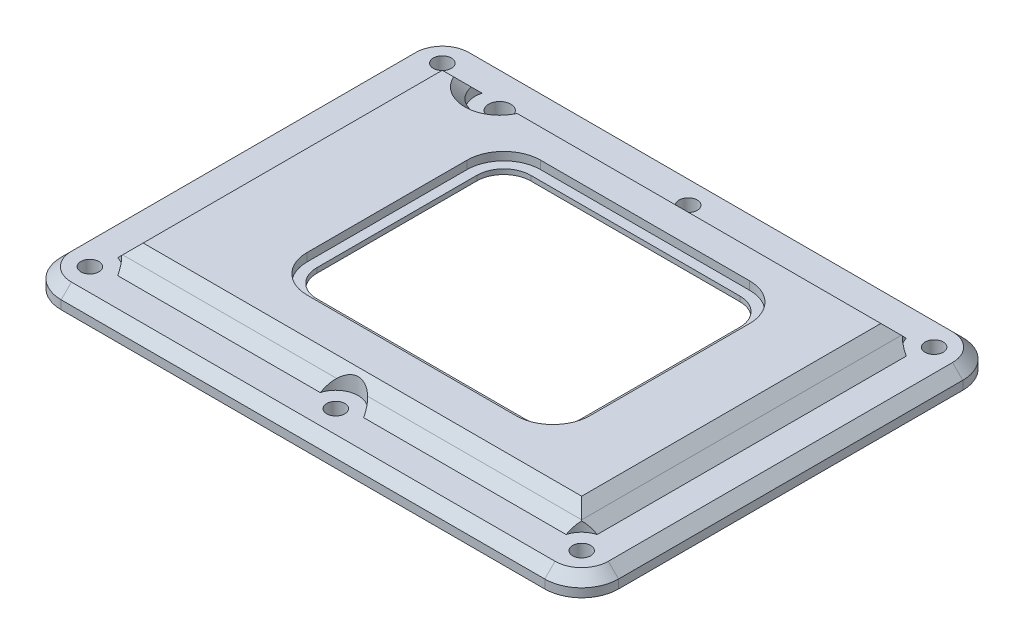
SolidWorks part; units mm, degrees
ref_plane "前视基准面" through (0, 0, 0) normal (0, 0, 1) x (1, 0, 0)
ref_plane "上视基准面" through (0, 0, 0) normal (0, 1, 0) x (1, 0, 0)
ref_plane "右视基准面" through (0, 0, 0) normal (1, 0, 0) x (0, 0, -1)
other "Configuration Table"
sketch "草图1" plane through (0, 0, 0) normal (0, 1, 0) x (1, 0, 0)
  line L1 (0, 0) -> (60, 0) construction
  line L2 (0, 0) -> (0, -43) construction
  line L3 (0, -43) -> (60, -43) construction
  line L4 (60, 0) -> (60, -43) construction
  line L5 (-4, 4) -> (64, 4)
  line L6 (-4, 4) -> (-4, -47)
  line L7 (-4, -47) -> (64, -47)
  line L8 (64, 4) -> (64, -47)
  line L9 (4, -4) -> (56, -4)
  line L10 (4, -4) -> (4, -39)
  line L11 (4, -39) -> (56, -39)
  line L12 (56, -4) -> (56, -39)
  circle A0 centre (0, 0) radius 1.1
  circle A1 centre (60, 0) radius 1.1
  circle A2 centre (30, 0) radius 1.1
  circle A3 centre (0, -43) radius 1.1
  circle A4 centre (60, -43) radius 1.1
  circle A5 centre (30, -43) radius 1.1
  dimension "D2" = 2.2
  dimension "D4" = 4
  dimension "D1" = 60
  dimension "D3" = 43
  dimension "D5" = 4
  dimension "D6" = 4
  dimension "D7" = 4
  dimension "D8" = 4
  dimension "D9" = 4
  dimension "D10" = 4
  dimension "D11" = 4
extrude "凸台-拉伸1" add sketch "草图1" along normal blind 2.31
sketch "草图2" plane through (0, 2.31, 0) normal (0, 1, 0) x (1, 0, 0)
  line L0 (2, -2) -> (58, -2)
  line L1 (4, -4) -> (56, -4)
  line L2 (4, -4) -> (4, -39)
  line L3 (4, -39) -> (56, -39)
  line L4 (56, -4) -> (56, -39)
  line L5 (58, -2) -> (58, -41)
  line L6 (2, -41) -> (58, -41)
  line L7 (2, -2) -> (2, -41)
  dimension "D1" = 2
extrude "凸台-拉伸2" add sketch "草图2" along normal blind 1.5
sketch "草图3" plane through (0, 2.31, 0) normal (0, 1, 0) x (1, 0, 0)
  circle A0 centre (8.5, -1.5) radius 1.35
  circle A2 centre (8.5, -1.5) radius 1.6 construction
  dimension "D2" = 2.7
extrude "切除-拉伸1" cut sketch "草图3" against normal up to next
sketch "草图4" plane through (0, 3.81, 0) normal (0, 1, 0) x (1, 0, 0)
  line L0 (4, -4) -> (4, -39) construction
  line L1 (14.25, -35.25) -> (48.75, -35.25)
  line L2 (14.25, -35.25) -> (14.25, -6.75)
  line L3 (14.25, -6.75) -> (48.75, -6.75)
  line L4 (48.75, -35.25) -> (48.75, -6.75)
  line L6 (56, -39) -> (56, -4) construction
  line L7 (56, -4) -> (4, -4) construction
  line L8 (4, -39) -> (56, -39) construction
  line L17 (2, -2) -> (2, -41)
  line L18 (2, -41) -> (58, -41)
  line L19 (58, -41) -> (58, -2)
  line L20 (58, -2) -> (2, -2)
  line L21 (2, -2) -> (2, -41)
  line L22 (2, -41) -> (58, -41)
  line L23 (58, -41) -> (58, -2)
  line L24 (58, -2) -> (2, -2)
  dimension "D1" = 10.25
  dimension "D2" = 7.25
  dimension "D3" = 2.75
  dimension "D4" = 3.75
  dimension "D5" = 0
extrude "凸台-拉伸3" add sketch "草图4" along normal blind 1
sketch "草图5" plane through (0, 2.31, 0) normal (0, 1, 0) x (1, 0, 0)
  circle A0 centre (8.5, -1.5) radius 3
  dimension "D1" = 6
extrude "切除-拉伸2" cut sketch "草图5" along normal up to next
sketch "草图6" plane through (0, 3.81, 0) normal (0, -1, 0) x (1, 0, 0)
  line L0 (5.3775, 4) -> (6.8417, 4)
  line L1 (6.8417, 4) -> (4, 4) construction
  line L2 (10.1583, 4) -> (11.6225, 4)
  arc A0 (11.6225, 4) -> (5.3775, 4) centre (8.5, 1.5) ccw
  arc A1 (10.1583, 4) -> (6.8417, 4) centre (8.5, 1.5) ccw construction
  arc A2 (10.1583, 4) -> (6.8417, 4) centre (8.5, 1.5) ccw
  dimension "D1" = 8
extrude "凸台-拉伸4" add sketch "草图6" along normal blind 2.5
sketch "草图7" plane through (0, 1.31, 0) normal (0, -1, 0) x (1, 0, 0)
  line L0 (5.3775, 4) -> (11.6225, 4)
  arc A0 (11.6225, 4) -> (5.3775, 4) centre (8.5, 1.5) ccw construction
  arc A1 (11.6225, 4) -> (5.3775, 4) centre (8.5, 1.5) ccw
extrude "凸台-拉伸5" add sketch "草图7" against normal up to surface (1 mm away) up to face at (19.25, 2.31, 12.2837)
fillet "圆角1" radius 4.5 8 edges at (48.75, 4.31, 6.75) (48.75, 4.31, 35.25) (14.25, 4.31, 35.25) (14.25, 4.31, 6.75) (-4, 1.155, 47) (64, 1.155, 47) (64, 1.155, -4) (-4, 1.155, -4)
chamfer "倒角1" distance 1.25 angle 45 19 edges at (58, 4.81, 21.5) (30, 4.81, 41) (2, 4.81, 21.5) (3.771, 4.81, 2) (34.729, 4.81, 2) (8.5, 4.81, 4.5) (3.771, 2.31, 2) (34.729, 2.31, 2) (2, 2.31, 21.5) (30, 2.31, 41) (58, 2.31, 21.5) (64, 2.31, 21.5) (62.682, 2.31, -2.682) (62.682, 2.31, 45.682) (30, 2.31, -4) (30, 2.31, 47) (-2.682, 2.31, -2.682) (-2.682, 2.31, 45.682) (-4, 2.31, 21.5)
sketch "草图9" plane through (0, 2.31, 0) normal (0, 1, 0) x (1, 0, 0)
  circle A0 centre (0, 0) radius 2.75
  circle A1 centre (30, 0) radius 2.75
  circle A2 centre (60, 0) radius 2.75
  circle A3 centre (60, -43) radius 2.75
  circle A4 centre (30, -43) radius 2.75
  circle A5 centre (0, -43) radius 2.75
  dimension "D1" = 5.5
extrude "切除-拉伸3" cut sketch "草图9" along normal up to next
sketch "草图10" plane through (0, 3.81, 0) normal (0, -1, 0) x (1, 0, 0)
  line L21 (47.55, 11.25) -> (47.55, 30.75)
  line L22 (18.75, 7.95) -> (44.25, 7.95)
  line L23 (15.45, 30.75) -> (15.45, 11.25)
  line L24 (44.25, 34.05) -> (18.75, 34.05)
  line L25 (47.55, 11.25) -> (47.55, 30.75)
  line L26 (18.75, 7.95) -> (44.25, 7.95)
  line L27 (15.45, 30.75) -> (15.45, 11.25)
  line L28 (44.25, 34.05) -> (18.75, 34.05)
  line L45 (44.25, 37.25) -> (18.75, 37.25)
  line L46 (50.75, 11.25) -> (50.75, 30.75)
  line L47 (18.75, 4.75) -> (44.25, 4.75)
  line L48 (12.25, 30.75) -> (12.25, 11.25)
  line L49 (44.25, 37.25) -> (18.75, 37.25)
  line L50 (50.75, 11.25) -> (50.75, 30.75)
  line L51 (18.75, 4.75) -> (44.25, 4.75)
  line L52 (12.25, 30.75) -> (12.25, 11.25)
  arc A18 (44.25, 7.95) -> (47.55, 11.25) centre (44.25, 11.25) ccw
  arc A19 (47.55, 30.75) -> (44.25, 34.05) centre (44.25, 30.75) ccw
  arc A20 (15.45, 11.25) -> (18.75, 7.95) centre (18.75, 11.25) ccw
  arc A21 (18.75, 34.05) -> (15.45, 30.75) centre (18.75, 30.75) ccw
  arc A22 (44.25, 7.95) -> (47.55, 11.25) centre (44.25, 11.25) ccw
  arc A23 (47.55, 30.75) -> (44.25, 34.05) centre (44.25, 30.75) ccw
  arc A24 (15.45, 11.25) -> (18.75, 7.95) centre (18.75, 11.25) ccw
  arc A25 (18.75, 34.05) -> (15.45, 30.75) centre (18.75, 30.75) ccw
  arc A46 (50.75, 30.75) -> (44.25, 37.25) centre (44.25, 30.75) ccw
  arc A47 (44.25, 4.75) -> (50.75, 11.25) centre (44.25, 11.25) ccw
  arc A48 (12.25, 11.25) -> (18.75, 4.75) centre (18.75, 11.25) ccw
  arc A49 (18.75, 37.25) -> (12.25, 30.75) centre (18.75, 30.75) ccw
  arc A50 (50.75, 30.75) -> (44.25, 37.25) centre (44.25, 30.75) ccw
  arc A51 (44.25, 4.75) -> (50.75, 11.25) centre (44.25, 11.25) ccw
  arc A52 (12.25, 11.25) -> (18.75, 4.75) centre (18.75, 11.25) ccw
  arc A53 (18.75, 37.25) -> (12.25, 30.75) centre (18.75, 30.75) ccw
  dimension "D1" = 1.2
  dimension "D2" = 2
extrude "凸台-拉伸6" add sketch "草图10" along normal blind 0.6
